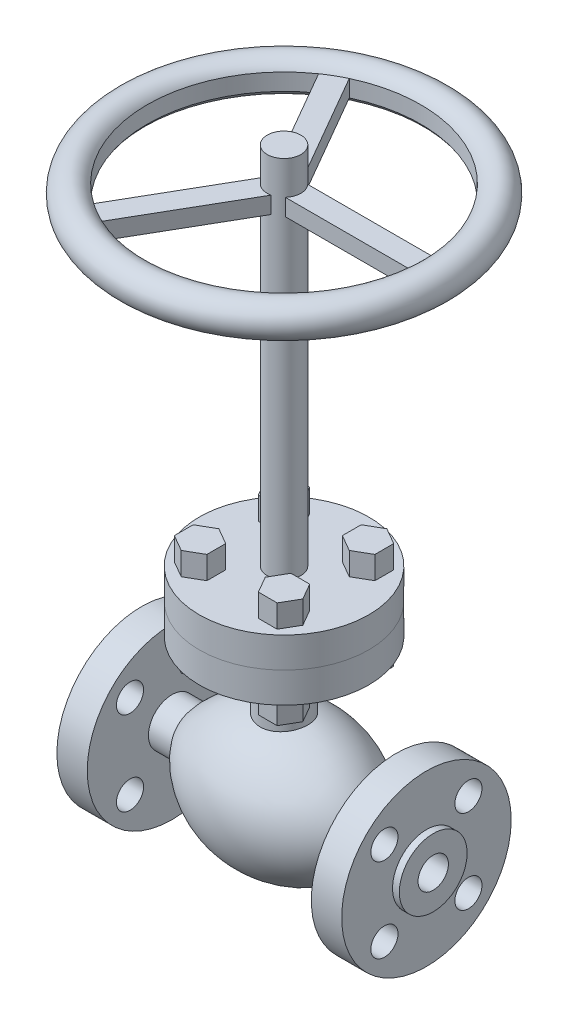
SolidWorks part; units mm, degrees
ref_plane "Front Plane" through (0, 0, 0) normal (0, 0, 1) x (1, 0, 0)
ref_plane "Top Plane" through (0, 0, 0) normal (0, 1, 0) x (1, 0, 0)
ref_plane "Right Plane" through (0, 0, 0) normal (1, 0, 0) x (0, 0, -1)
sketch "Flow Extrude Sketch" plane through (0, 0, 0) normal (0, 0, 1) x (1, 0, 0)
  line L0 (-321.7404, 0) -> (110.5039, 0) construction
  line L1 (0, 0) -> (0, 85.3189) construction
  line L2 (83.82, 22.098) -> (139.7, 22.098)
  line L3 (-139.7, 22.098) -> (-83.82, 22.098)
  line L4 (-139.7, 22.098) -> (-139.7, 0)
  line L5 (-139.7, 0) -> (139.7, 0)
  line L6 (139.7, 22.098) -> (139.7, 0)
  arc A1 (-83.82, 22.098) -> (83.82, 22.098) centre (0, -42.0495) cw
  point P13 (0, 63.5)
  dimension "d+2*t" = 44.196
  dimension "A" = 279.4
  dimension "A*.6" = 167.64
  dimension "O*.8" = 127
revolve "Flow Extrude" add sketch "Flow Extrude Sketch" angle 360 about L0
sketch "Flow Flange Sketch" plane through (139.7, 0, 0) normal (1, 0, 0) x (0, 0, -1)
  circle A0 centre (0, 0) radius 79.375
  dimension "O" = 158.75
extrude "Flow Flange" add sketch "Flow Flange Sketch" against normal blind 34.798
sketch "Hub Cut Sketch" plane through (139.7, 0, 0) normal (1, 0, 0) x (0, 0, -1)
  circle A0 centre (0, 0) radius 31.75
  dimension "R" = 63.5
extrude "Hub Cut" cut sketch "Hub Cut Sketch" against normal blind 6.35 flip side to cut
sketch "Bolt Hole Sketch" plane through (139.7, 0, 0) normal (1, 0, 0) x (0, 0, -1)
  line L0 (0, 0) -> (0, 227.9139) construction
  line L1 (0, 0) -> (159.6271, 159.6271) construction
  circle A0 centre (0, 0) radius 55.626 construction
  circle A1 centre (39.3335, 39.3335) radius 12.7
  dimension "BC" = 111.252
  dimension "DH" = 25.4
  dimension "Angle" = 45
extrude "Bolt Hole" cut sketch "Bolt Hole Sketch" against normal up to next
pattern_circular "Bolt Hole Pattern" count 4 every 90 about axis through (-321.7404, 0, 0) along (1, 0, 0) of "Bolt Hole"
mirror "Flange Mirror" about plane through (0, 0, 0) normal (1, 0, 0) of "Flow Flange", "Bolt Hole", "Bolt Hole Pattern", "Hub Cut"
sketch "Body Extrude Sketch" plane through (0, 0, 0) normal (0, 1, 0) x (1, 0, 0)
  line L1 (0, -96.6135) -> (0, 96.6135) construction
  circle A0 centre (0, 0) radius 22.319
  dimension "(d+2*t)*1.01" = 44.638
extrude "Body Extrude" add sketch "Body Extrude Sketch" along normal blind 122.047
sketch "Flange Bottom Sketch" plane through (0, 122.047, 0) normal (0, 1, 0) x (-1, 0, 0)
  circle A0 centre (0, 0) radius 79.375
  dimension "O" = 158.75
extrude "Flange Bottom" add sketch "Flange Bottom Sketch" along normal blind 28.448
sketch "Flange Top Sketch" plane through (0, 150.495, 0) normal (0, 1, 0) x (-1, 0, 0)
  circle A1 centre (0, 0) radius 79.375
  circle A2 centre (0, 0) radius 79.375
  dimension "D1" = 0
extrude "Flange Top" add sketch "Flange Top Sketch" along normal blind 28.448
ref_plane "Driver Plane" through (0, 481.076, 0) normal (0, 1, 0) x (-1, 0, 0)
sketch "Driver Path" plane through (0, 481.076, 0) normal (0, 1, 0) x (-1, 0, 0)
  circle A0 centre (0, 0) radius 157.48
  dimension "D" = 314.96
sketch "Driver Profile" plane through (0, 0, 0) normal (0, 0, 1) x (1, 0, 0)
  line L0 (157.48, 481.076) -> (-157.48, 481.076) construction
  line L1 (-128.0938, 488.95) -> (0, 488.95)
  line L2 (157.48, 481.076) -> (-157.48, 481.076) construction
  line L3 (-128.0938, 473.202) -> (0, 473.202)
  line L4 (0, 488.95) -> (0, 473.202)
  arc A0 (-128.0938, 488.95) -> (-128.0938, 473.202) centre (-141.732, 481.076) ccw
  dimension "D1" = 15.748
  dimension "D/20" = 15.748
sweep "Driver Sweep" add profiles "Driver Profile" path "Driver Path"
sketch "Centre Support Sketch" plane through (0, 488.95, 0) normal (0, 1, 0) x (-1, 0, 0)
  circle A0 centre (0, 0) radius 15.748
  dimension "D/10" = 31.496
extrude "Centre Support" add sketch "Centre Support Sketch" against normal up to surface (310.007 mm away) and the other way blind 31.496 up to face at (0, 178.943, 79.375)
sketch "Driver Cut Sketch" plane through (0, 488.95, 0) normal (0, 1, 0) x (-1, 0, 0)
  line L0 (0, 0) -> (0, 113.8697) construction
  line L1 (0, 0) -> (-104.7757, 0) construction
  line L2 (54.7393, 115.8086) -> (-3.2232, 15.4146)
  line L3 (-127.6629, -10.4987) -> (-11.7379, -10.4987)
  line L4 (72.9235, 105.31) -> (14.961, 4.916)
  line L5 (-127.6629, 10.4987) -> (-11.7379, 10.4987)
  line L6 (72.9235, -105.31) -> (14.961, -4.916)
  line L7 (54.7393, -115.8086) -> (-3.2232, -15.4146)
  circle A0 centre (0, 0) radius 128.0938 construction
  arc A1 (54.7393, 115.8086) -> (-127.6629, 10.4987) centre (0, 0) ccw
  circle A2 centre (0, 0) radius 15.748 construction
  arc A3 (-11.7379, -10.4987) -> (-3.2232, -15.4146) centre (0, 0) ccw
  arc A4 (-3.2232, 15.4146) -> (-11.7379, 10.4987) centre (0, 0) ccw
  arc A5 (14.961, -4.916) -> (14.961, 4.916) centre (0, 0) ccw
  arc A6 (72.9235, -105.31) -> (72.9235, 105.31) centre (0, 0) ccw
  arc A7 (-127.6629, -10.4987) -> (54.7393, -115.8086) centre (0, 0) ccw
  dimension "D/30" = 10.4987
extrude "Driver Cut" cut sketch "Driver Cut Sketch" against normal up to surface (15.748 mm away) up to face at (0, 473.202, 15.748)
sketch "ID Sketch" plane through (139.7, 0, 0) normal (-1, 0, 0) x (0, 0, 1)
  circle A0 centre (0, 0) radius 14.224
  dimension "d" = 28.448
extrude "ID Cut" cut sketch "ID Sketch" along normal through all
ref_plane "Bolt Plane" through (0, 200.279, 0) normal (0, 1, 0) x (-1, 0, 0)
sketch "Bolt Sketch" plane through (0, 200.279, 0) normal (0, 1, 0) x (-1, 0, 0)
  line L0 (0, 0) -> (-97.4469, -97.4469) construction
  line L1 (0, 0) -> (-142.2485, 0) construction
  line L2 (-39.3335, -21.7359) -> (-54.5735, -30.5347)
  line L3 (-54.5735, -30.5347) -> (-54.5735, -48.1323)
  line L4 (-54.5735, -48.1323) -> (-39.3335, -56.9312)
  line L5 (-39.3335, -56.9312) -> (-24.0935, -48.1323)
  line L6 (-24.0935, -48.1323) -> (-24.0935, -30.5347)
  line L7 (-24.0935, -30.5347) -> (-39.3335, -21.7359)
  circle A0 centre (0, 0) radius 55.626 construction
  circle A2 centre (-39.3335, -39.3335) radius 15.24 construction
  dimension "BC" = 111.252
  dimension "DH*1.2" = 30.48
  dimension "Angle" = 45
extrude "Bolt" add sketch "Bolt Sketch" against normal blind 99.568
pattern_circular "Bolt Pattern" count 4 every 90 about axis through (0, 150.495, 0) along (0, -1, 0) of "Bolt"
sketch "Sketch1" plane through (0, 0, 0) normal (0, 0, 1) x (1, 0, 0)
  line L1 (79.375, 150.495) -> (-79.375, 150.495)
  line L2 (79.375, 150.495) -> (-79.375, 150.495)
  dimension "D1" = 0
split line "Split Line1"
sketch "CPointSketch" plane through (0, 0, 0) normal (0, 0, 1) x (1, 0, 0)
  line L2 (139.7, -22.098) -> (139.7, 22.098) construction
  line L3 (-139.7, 22.098) -> (-139.7, -22.098) construction
  point P0 (-139.7, 0)
  point P1 (139.7, 0)
  point P4 (0, 0)
other "CPoint1" parameters "Diameter"=31.75, "StubLength"=0
ref_axis "Axis1" through (149.7, 0, 0) along (-1, 0, 0)
other "CPoint2" parameters "Diameter"=31.75, "StubLength"=0
ref_axis "Axis2" through (-149.7, 0, 0) along (1, 0, 0)
other "RPoint1"
equation "\"D1@Driver Profile\" = \"D/20@Driver Profile\""
equation "\"D2@Centre Support\" = \"D/10@Centre Support Sketch\""
